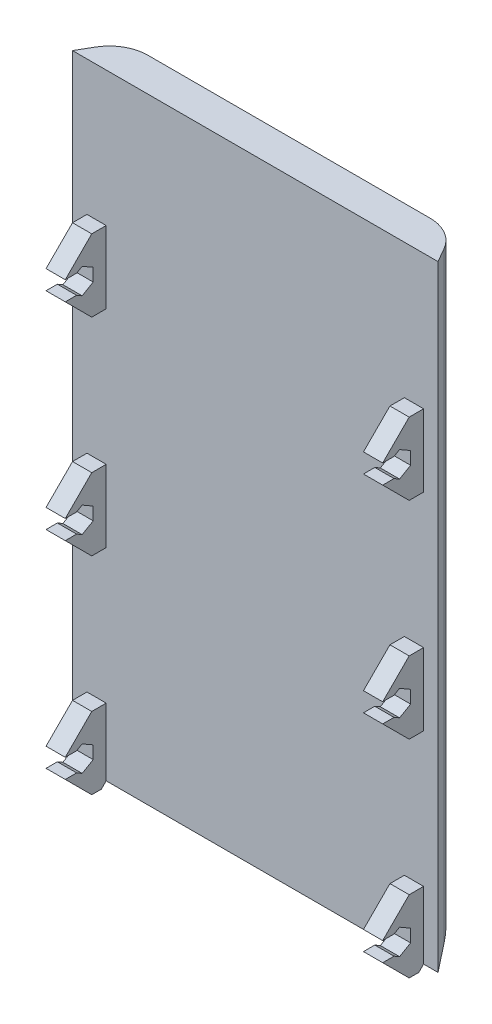
SolidWorks part; units mm, degrees
ref_plane "Front Plane" through (0, 0, 0) normal (0, 0, 1) x (1, 0, 0)
ref_plane "Top Plane" through (0, 0, 0) normal (0, 1, 0) x (1, 0, 0)
ref_plane "Right Plane" through (0, 0, 0) normal (1, 0, 0) x (0, 0, -1)
sketch "Sketch1" plane through (0, 0, 0) normal (0, 1, 0) x (1, 0, 0)
  line L0 (-9.2151, 0) -> (-9.2151, -10)
  line L1 (-9.2151, -10) -> (-5.2151, -10)
  line L2 (-5.2151, -10) -> (-5.2151, 0)
  line L3 (-5.2151, 0) -> (56.7849, 0)
  line L4 (56.7849, 0) -> (56.7849, -10)
  line L5 (56.7849, -10) -> (60.7849, -10)
  line L6 (60.7849, -10) -> (60.7849, 0)
  line L7 (60.7849, 0) -> (63.7849, 0)
  line L8 (-9.2151, 0) -> (-12.2151, 0)
  line L9 (-12.2151, 0) -> (-8.1737, 7)
  line L10 (-8.1737, 7) -> (59.7434, 7)
  line L11 (59.7434, 7) -> (63.7849, 0)
  line L12 (25.7849, 7) -> (25.7849, 0) construction
  dimension "D1" = 3
  dimension "D2" = 10
  dimension "D3" = 70
  dimension "D4" = 7
  dimension "D5" = 4
  dimension "D6" = 60
extrude "Boss-Extrude1" add sketch "Sketch1" along normal blind 129
sketch "Sketch4" plane through (60.7849, 0, 0) normal (1, 0, 0) x (0, 0, -1)
  line L0 (0, 129) -> (0, 0) construction
  line L1 (-37.5185, 129) -> (0, 129)
  line L2 (-37.5185, 129) -> (-37.5185, 101)
  line L3 (-37.5185, 101) -> (0, 101)
  line L4 (0, 129) -> (0, 101)
  line L5 (-37.5185, 129) -> (0, 101) construction
  line L6 (-37.5185, 101) -> (0, 129) construction
  line L7 (-10, 129) -> (0, 129) construction
  point P0 (-18.7592, 115)
  dimension "D1" = 28
extrude "Cut-Extrude1" cut sketch "Sketch4" against normal through all
sketch "Sketch5" plane through (60.7849, 0, 0) normal (1, 0, 0) x (0, 0, -1)
  line L0 (0, 129) -> (0, 0) construction
  line L1 (-33.3149, 86) -> (0, 86)
  line L2 (-33.3149, 86) -> (-33.3149, 58)
  line L3 (-33.3149, 58) -> (0, 58)
  line L4 (0, 86) -> (0, 58)
  line L5 (-33.3149, 86) -> (0, 58) construction
  line L6 (-33.3149, 58) -> (0, 86) construction
  line L7 (-10, 101) -> (0, 101) construction
  point P0 (-16.6574, 72)
  dimension "D1" = 28
  dimension "D2" = 15
extrude "Cut-Extrude2" cut sketch "Sketch5" against normal through all
sketch "Sketch6" plane through (0, 0, 0) normal (1, 0, 0) x (0, 0, -1)
  line L0 (-10, 101) -> (-10, 86) construction
  line L1 (-2.7, 94.8279) -> (-5, 96.1558)
  line L2 (-5, 96.1558) -> (-7.3, 94.8279)
  line L3 (-7.3, 94.8279) -> (-7.3, 92.1721)
  line L4 (-7.3, 92.1721) -> (-5, 90.8442)
  line L5 (-5, 90.8442) -> (-2.7, 92.1721)
  line L6 (-2.7, 92.1721) -> (-2.7, 94.8279)
  line L7 (-10, 101) -> (0, 101) construction
  line L8 (-6.15, 95.4919) -> (-10, 95.4919)
  line L9 (-6.15, 91.5081) -> (-10, 91.5081)
  line L10 (-10, 91.5081) -> (-10, 95.4919)
  circle A1 centre (-5, 93.5) radius 2.3 construction
  dimension "D1" = 4.6
  dimension "D2" = 7.5
  dimension "D3" = 5
extrude "Cut-Extrude3" cut sketch "Sketch6" against normal through all and the other way through all contours L10 L9 L4 L3 L2 L8 | L5 L6 L1 L2 L3 L4 region at (0, 93.5, 5) region at (0, 93.5, 8.5351)
pattern_linear "LPattern1" count 4 spacing 43 along (0, -1, 0) of "Cut-Extrude2", "Cut-Extrude3"
chamfer "Chamfer6" distance 8 angle 45 1 edges at (25.7849, 0, -7)
fillet "Fillet1" radius 8 2 edges at (-8.1737, 68.5, -7) (59.7434, 68.5, -7)
chamfer "Chamfer5" distance 7 angle 45 12 edges at (58.7849, 101, 10) (58.7849, 86, 10) (-7.2151, 101, 10) (-7.2151, 86, 10) (-7.2151, 58, 10) (-7.2151, 43, 10) (58.7849, 58, 10) (58.7849, 43, 10) (58.7849, 15, 10) (58.7849, 0, 10) (-7.2151, 0, 10) (-7.2151, 15, 10)
sketch "Sketch7" plane through (0, 0, -7) normal (0, 0, -1) x (-1, 0, 0)
  line L0 (-40.1246, 129) -> (-40.1246, 21.6303) construction
  line L1 (-55.1246, 129) -> (3.5549, 129) construction
  line L3 (-55.1246, 129) -> (-55.1246, 8) construction
  text T0 "ROAB LAB" font "VALORANT" height in points 48
  dimension "D1" = 15
extrude "Cut-Extrude4" cut sketch "Sketch7" against normal blind 1
sketch "Sketch8" plane through (0, 0, -7) normal (0, 0, -1) x (-1, 0, 0)
  line L0 (-5.9451, 109.5431) -> (-17.4451, 109.5431)
  line L1 (-17.4451, 109.5431) -> (-17.4451, 107.0431)
  line L2 (-17.4451, 107.0431) -> (-5.9451, 107.0431)
  line L3 (-5.9451, 107.0431) -> (-5.9451, 102.7931)
  line L4 (-5.9451, 102.7931) -> (-3.4451, 102.7931)
  line L5 (-3.4451, 102.7931) -> (-3.4451, 113.7931)
  line L6 (-3.4451, 113.7931) -> (-5.9451, 113.7931)
  line L7 (-5.9451, 113.7931) -> (-5.9451, 109.5431)
  line L8 (-3.4451, 100.2931) -> (-3.4451, 97.7931)
  line L9 (-3.4451, 97.7931) -> (-17.4451, 97.7931)
  line L10 (-17.4451, 97.7931) -> (-17.4451, 100.2931)
  line L11 (-17.4451, 100.2931) -> (-3.4451, 100.2931)
  line L12 (-3.4451, 113.7931) -> (-3.4451, 31.6687) construction
  line L13 (-17.4451, 109.5431) -> (-17.4451, 29.6442) construction
  line L14 (-3.4451, 95.2931) -> (-17.4451, 95.2931)
  line L15 (-17.4451, 95.2931) -> (-17.4451, 92.7931)
  line L16 (-17.4451, 92.7931) -> (-8.4451, 92.7931)
  line L17 (-8.4451, 92.7931) -> (-17.4451, 87.597)
  line L18 (-17.4451, 87.597) -> (-17.4451, 85.097)
  line L19 (-17.4451, 85.097) -> (-8.4451, 85.097)
  line L20 (-8.4451, 85.097) -> (-17.4451, 79.9008)
  line L21 (-17.4451, 79.9008) -> (-17.4451, 79.5141)
  line L22 (-17.4451, 79.5141) -> (-13.115, 79.5141)
  line L23 (-13.115, 79.5141) -> (-3.4451, 85.097)
  line L24 (-3.4451, 85.097) -> (-3.4451, 87.597)
  line L25 (-3.4451, 87.597) -> (-12.4451, 87.597)
  line L26 (-12.4451, 87.597) -> (-3.4451, 92.7931)
  line L27 (-3.4451, 92.7931) -> (-3.4451, 95.2931)
  line L28 (-3.4451, 85.097) -> (-17.4451, 77.0141) construction
  line L29 (-17.4451, 77.0141) -> (-3.4451, 77.0141)
  line L30 (-3.4451, 77.0141) -> (-3.4451, 74.5141)
  line L31 (-3.4451, 74.5141) -> (-17.4451, 66.4312)
  line L32 (-17.4451, 66.4312) -> (-17.4451, 69.3179)
  line L33 (-17.4451, 69.3179) -> (-15.1951, 70.617)
  line L34 (-15.1951, 70.617) -> (-17.4451, 74.5141)
  line L35 (-17.4451, 74.5141) -> (-17.4451, 77.0141)
  line L36 (-8.4451, 74.5141) -> (-13.0301, 71.867)
  line L37 (-14.5584, 74.5141) -> (-8.4451, 74.5141)
  line L38 (-14.5584, 74.5141) -> (-13.0301, 71.867)
  line L39 (-3.4451, 68.9312) -> (-8.115, 68.9312)
  line L40 (-8.115, 68.9312) -> (-12.4451, 66.4312)
  line L41 (-12.4451, 66.4312) -> (-8.4451, 66.4312)
  line L42 (-8.4451, 66.4312) -> (-17.4451, 61.235)
  line L43 (-17.4451, 61.235) -> (-17.4451, 58.735)
  line L44 (-17.4451, 58.735) -> (-3.4451, 58.735)
  line L45 (-3.4451, 58.735) -> (-3.4451, 61.235)
  line L46 (-3.4451, 61.235) -> (-12.4451, 61.235)
  line L47 (-12.4451, 61.235) -> (-3.4451, 66.4312)
  line L48 (-3.4451, 66.4312) -> (-3.4451, 68.9312)
  line L49 (-3.4451, 56.235) -> (-3.4451, 53.735)
  line L50 (-3.4451, 53.735) -> (-9.4451, 53.735)
  line L51 (-9.4451, 53.735) -> (-9.4451, 47.735)
  line L52 (-9.4451, 47.735) -> (-3.4451, 47.735)
  line L53 (-3.4451, 47.735) -> (-3.4451, 45.235)
  line L54 (-3.4451, 45.235) -> (-17.4451, 45.235)
  line L55 (-17.4451, 45.235) -> (-17.4451, 47.735)
  line L56 (-17.4451, 47.735) -> (-11.9451, 47.735)
  line L57 (-11.9451, 47.735) -> (-11.9451, 53.735)
  line L58 (-11.9451, 53.735) -> (-17.4451, 53.735)
  line L59 (-17.4451, 53.735) -> (-17.4451, 56.235)
  line L60 (-17.4451, 56.235) -> (-3.4451, 56.235)
  line L61 (-39.7028, 113.7931) -> (-27.8309, 113.7931) construction
  line L62 (3.5549, 8) -> (3.5549, 129) construction
  dimension "D1" = 2.5
  dimension "D2" = 14
  dimension "D3" = 11
  dimension "D4" = 2.5
  dimension "D5" = 2.5
  dimension "D6" = 2.5
  dimension "D7" = 30
  dimension "D8" = 2.5
  dimension "D9" = 2.5
  dimension "D10" = 60
  dimension "D11" = 2.5
  dimension "D12" = 2.5
  dimension "D13" = 30
  dimension "D14" = 60
  dimension "D15" = 2.5
  dimension "D16" = 2.5
  dimension "D17" = 2.5
  dimension "D18" = 2.5
  dimension "D19" = 2.5
  dimension "D20" = 2.5
  dimension "D21" = 2.5
  dimension "D22" = 30
  dimension "D23" = 2.5
  dimension "D24" = 11
  dimension "D25" = 6
  dimension "D26" = 2.5
  dimension "D27" = 7
extrude "Cut-Extrude5" cut sketch "Sketch8" against normal blind 1
